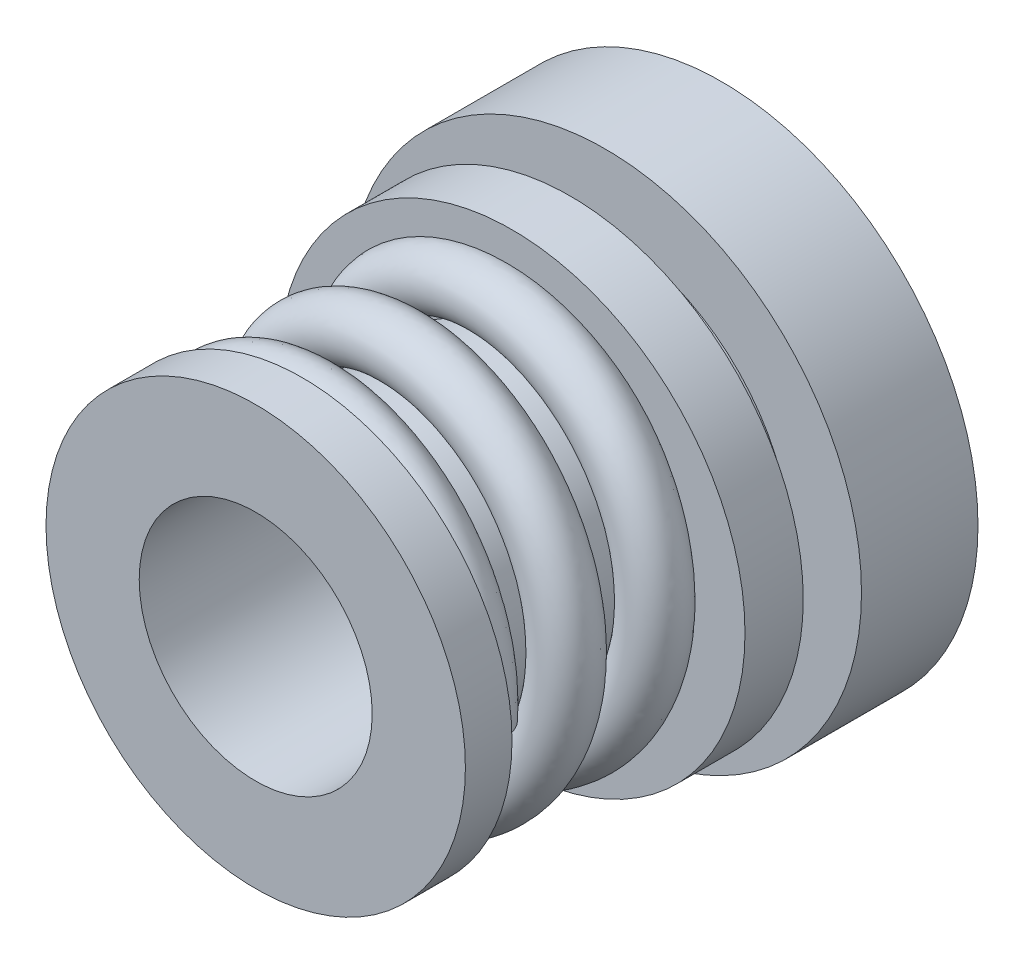
SolidWorks part; units mm, degrees
ref_plane "Alzado" through (0, 0, 0) normal (0, 0, 1) x (1, 0, 0)
ref_plane "Planta" through (0, 0, 0) normal (0, 1, 0) x (1, 0, 0)
ref_plane "Vista lateral" through (0, 0, 0) normal (1, 0, 0) x (0, 0, -1)
sketch "Croquis2" plane through (0, 0, 0) normal (0, 1, 0) x (1, 0, 0)
  line L0 (0, 0) -> (0, 18) construction
  line L1 (-5, 18) -> (-11, 18)
  line L2 (-11, 18) -> (-11, 13)
  line L3 (-11, 13) -> (-8, 13)
  line L4 (-8, 13) -> (-8, 12)
  line L5 (-8.45, 11.5) -> (-10, 11.5)
  line L6 (-10, 11.5) -> (-10, 9)
  line L7 (-10, 9) -> (-6, 9)
  line L8 (-6, 9) -> (-6, 0)
  line L9 (-6, 0) -> (-9, 0)
  line L10 (-9, 0) -> (-9, -2)
  line L11 (-9, -2) -> (-5, -2)
  line L12 (0, 0) -> (0, -2) construction
  line L13 (-5, 18) -> (-5, -2)
  line L14 (-5, 18) -> (0, 18) construction
  line L15 (-5, -2) -> (0, -2) construction
  arc A0 (-8, 12) -> (-8.45, 11.5) centre (-8.5028, 12) cw
  dimension "D1" = 11
  dimension "D2" = 5
  dimension "D3" = 15
  dimension "D4" = 5
  dimension "D5" = 4
  dimension "D6" = 1.5
  dimension "D7" = 2
  dimension "D8" = 6
  dimension "D9" = 9
  dimension "D10" = 1
  dimension "D11" = 3
  dimension "D12" = 10
revolve "Revolución1" add sketch "Croquis2" angle 360 about L0
sketch "Croquis3" plane through (0, 0, 0) normal (0, 0, -1) x (-1, 0, 0)
  circle A0 centre (0, 0) radius 7.5
  dimension "D1" = 15
curve "Hélice/Espiral1" pitch 3.8 height 9.5 radius 7.5 left hand yes centre (0, 0, 0) axis (0, 0, -1) start towards (-1, 0, 0)
sketch "Croquis4" plane through (0, 0, 0) normal (0, 1, 0) x (1, 0, 0)
  line L0 (9, 0) -> (-9, 0) construction
  circle A0 centre (7.5, 0) radius 1.2261
  spline S0 degree 3 poles (7.5, 0) (7.5, 0.0787) (7.1095, 0.2377) (5.4414, 0.4749) (2.9448, 0.7125) (0, 0.95) (-2.9448, 1.1875) (-5.4414, 1.425) (-7.1095, 1.6625) (-7.6953, 1.9) (-7.1095, 2.1375) (-5.4414, 2.375) (-2.1127, 2.6917) (2.1127, 3.0083) (5.4414, 3.325) (7.1095, 3.5625) (7.6953, 3.8) (7.1095, 4.0375) (5.4414, 4.275) (2.1127, 4.5917) (-2.1127, 4.9083) (-5.4414, 5.225) (-7.1095, 5.4625) (-7.6953, 5.7) (-7.1095, 5.9375) (-5.4414, 6.175) (-2.1127, 6.4917) (2.1127, 6.8083) (5.4414, 7.125) (7.1095, 7.3625) (7.6953, 7.6) (7.1095, 7.8375) (5.4414, 8.075) (2.9448, 8.3125) (0, 8.55) (-2.9448, 8.7875) (-5.4414, 9.0251) (-7.1095, 9.2623) (-7.5, 9.4213) (-7.5, 9.5) knots 0 0 0 0 0.025 0.05 0.075 0.1 0.125 0.15 0.175 0.2 0.225 0.25 0.275 0.325 0.35 0.375 0.4 0.425 0.45 0.475 0.525 0.55 0.575 0.6 0.625 0.65 0.675 0.725 0.75 0.775 0.8 0.825 0.85 0.875 0.9 0.925 0.95 0.975 1 1 1 1 construction
sweep "Barrer1" add profiles "Croquis4" path "Hélice/Espiral1"
